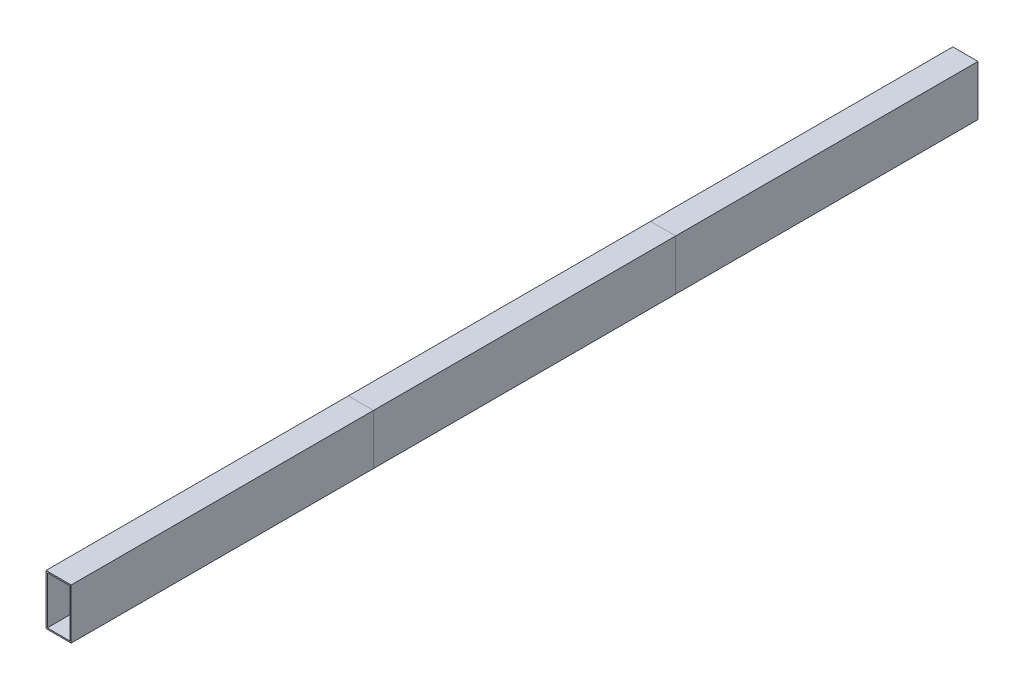
SolidWorks part; units mm, degrees
ref_plane "Спереди" through (0, 0, 0) normal (0, 0, 1) x (1, 0, 0)
ref_plane "Сверху" through (0, 0, 0) normal (0, 1, 0) x (1, 0, 0)
ref_plane "Справа" through (0, 0, 0) normal (1, 0, 0) x (0, 0, -1)
sketch "Эскиз1" plane through (0, 0, 0) normal (0, 0, 1) x (1, 0, 0)
  line L1 (-50, -100) -> (50, -100)
  line L2 (-50, -100) -> (-50, 100)
  line L3 (-50, 100) -> (50, 100)
  line L4 (50, -100) -> (50, 100)
  line L5 (-50, -100) -> (50, 100) construction
  line L6 (-50, 100) -> (50, -100) construction
  line L7 (-45, -95) -> (45, -95)
  line L8 (-45, -95) -> (-45, 95)
  line L9 (-45, 95) -> (45, 95)
  line L10 (45, -95) -> (45, 95)
  line L11 (-45, -95) -> (45, 95) construction
  line L12 (-45, 95) -> (45, -95) construction
  point P0 (0, 0)
  point P8 (0, 0)
  dimension "D1" = 100
  dimension "D2" = 200
  dimension "D3" = 90
  dimension "D4" = 190
extrude "Бобышка-Вытянуть1" add sketch "Эскиз1" along normal blind 1200
extrude "Бобышка-Вытянуть2" add sketch "Эскиз1<3>" along normal blind 1200 from surface separate body starting at face at (0, 0, 1200)
sketch "Эскиз1<3>" plane through (0, 0, 0) normal (0, 0, 1) x (1, 0, 0) same geometry as "Эскиз1"
extrude "Бобышка-Вытянуть3" add sketch "Эскиз1<4>" along normal blind 1200 from surface separate body starting at face at (0, 0, 2400)
sketch "Эскиз1<4>" plane through (0, 0, 0) normal (0, 0, 1) x (1, 0, 0) same geometry as "Эскиз1"
ref_point "Точка1"
ref_point "Точка2"
